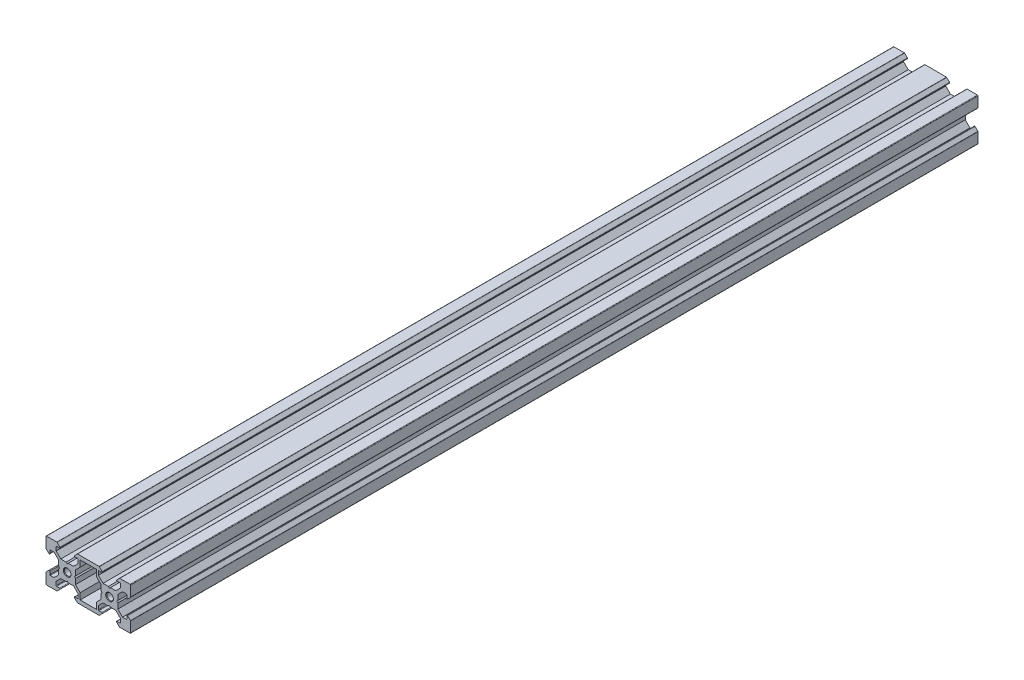
SolidWorks part; units mm, degrees
ref_plane "Alzado" through (0, 0, 0) normal (0, 0, 1) x (1, 0, 0)
ref_plane "Planta" through (0, 0, 0) normal (0, 1, 0) x (1, 0, 0)
ref_plane "Vista lateral" through (0, 0, 0) normal (1, 0, 0) x (0, 0, -1)
sketch "Croquis1" plane through (0, 0, 0) normal (0, 0, 1) x (1, 0, 0)
  line L0 (-10.0414, 10) -> (-10.0414, 8.2) construction
  line L1 (-13.8828, 8.2) -> (-6.2, 8.2)
  line L2 (-13.8828, -8.2) -> (-6.2, -8.2)
  line L4 (-4.8096, 9.9268) -> (-3.5096, 8.6268)
  line L5 (-3.6864, 8.2) -> (-5.0429, 8.2)
  line L6 (-5.2929, 7.95) -> (-5.2929, 6.2)
  line L13 (-14.8728, 8.2) -> (-16.6, 8.2)
  line L14 (-5.2929, 6.2) -> (-3.0929, 4)
  line L15 (-3.0929, 4) -> (-0.5828, 4)
  line L16 (-16.0828, 0.5) -> (-16.5828, 0)
  line L17 (-16.0828, 3.0101) -> (-16.0828, 0.5)
  line L18 (-13.8828, 5.2101) -> (-16.0828, 3.0101)
  line L19 (-13.8828, 8.2) -> (-13.8828, 5.2101)
  line L23 (-16.0828, -3.0101) -> (-16.0828, -0.5)
  line L24 (-16.0828, -0.5) -> (-16.5828, 0)
  line L25 (-13.8828, -5.2101) -> (-16.0828, -3.0101)
  line L26 (-13.8828, -8.2) -> (-13.8828, -5.2101)
  line L29 (-0.5828, 4) -> (-0.0828, 3.5)
  line L30 (-0.0828, 3.5) -> (0.4172, 4)
  line L31 (0.4172, 4) -> (2.9272, 4)
  line L32 (2.9272, 4) -> (5.1272, 6.2)
  line L33 (5.1272, 6.2) -> (5.1272, 7.95)
  line L34 (4.8772, 8.2) -> (3.5207, 8.2)
  line L35 (3.3439, 8.6268) -> (4.6439, 9.9268)
  line L36 (4.8207, 10) -> (9.6672, 10)
  line L37 (9.9172, 9.75) -> (9.9172, 4.9036)
  line L38 (9.8439, 4.7268) -> (8.5439, 3.4268)
  line L39 (8.1172, 3.6036) -> (8.1172, 4.9601)
  line L40 (7.8672, 5.2101) -> (6.1172, 5.2101)
  line L41 (6.1172, 5.2101) -> (3.9172, 3.0101)
  line L42 (3.9172, 3.0101) -> (3.9172, 0.5)
  line L43 (3.9172, 0.5) -> (3.4172, 0)
  line L44 (3.4172, 0) -> (3.9172, -0.5)
  line L45 (3.9172, -0.5) -> (3.9172, -3.0101)
  line L46 (3.9172, -3.0101) -> (6.1172, -5.2101)
  line L47 (6.1172, -5.2101) -> (7.8672, -5.2101)
  line L48 (8.1172, -4.9601) -> (8.1172, -3.6036)
  line L49 (8.5439, -3.4268) -> (9.8439, -4.7268)
  line L50 (9.9172, -4.9036) -> (9.9172, -9.75)
  line L51 (9.6672, -10) -> (4.8207, -10)
  line L52 (4.6439, -9.9268) -> (3.3439, -8.6268)
  line L53 (3.5207, -8.2) -> (4.8772, -8.2)
  line L54 (5.1272, -7.95) -> (5.1272, -6.2)
  line L55 (5.1272, -6.2) -> (2.9272, -4)
  line L56 (2.9272, -4) -> (0.4172, -4)
  line L57 (0.4172, -4) -> (-0.0828, -3.5)
  line L58 (-0.0828, -3.5) -> (-0.5828, -4)
  line L59 (-0.5828, -4) -> (-3.0929, -4)
  line L60 (-3.0929, -4) -> (-5.2929, -6.2)
  line L61 (-5.2929, -6.2) -> (-5.2929, -7.95)
  line L62 (-5.0429, -8.2) -> (-3.6864, -8.2)
  line L63 (-3.5096, -8.6268) -> (-4.8096, -9.9268)
  line L64 (-6.2, -8.2) -> (-6.2, -5.2101)
  line L65 (-6.2, -5.2101) -> (-4, -3.0101)
  line L66 (-4, -3.0101) -> (-4, -0.5)
  line L67 (-4, -0.5) -> (-3.5, 0)
  line L68 (-4, 0.5) -> (-3.5, 0)
  line L69 (-4, 3.0101) -> (-4, 0.5)
  line L70 (-6.2, 5.2101) -> (-4, 3.0101)
  line L71 (-6.2, 8.2) -> (-6.2, 5.2101)
  line L72 (-39.2829, 0) -> (29.3198, 0) construction
  line L73 (-20, 18.9047) -> (-20, -25.5585) construction
  line L74 (-0.0828, -25.5585) -> (-0.0828, 18.9047) construction
  line L164 (-26.2, 5.2101) -> (-24, 3.0101)
  line L165 (-24, 3.0101) -> (-24, 0.5)
  line L166 (-24, 0.5) -> (-23.5, 0)
  line L167 (-23.5, 0) -> (-24, -0.5)
  line L168 (-24, -0.5) -> (-24, -3.0101)
  line L169 (-24, -3.0101) -> (-26.2, -5.2101)
  line L170 (-26.2, -5.2101) -> (-27.95, -5.2101)
  line L171 (-28.2, -4.9601) -> (-28.2, -3.6036)
  line L172 (-28.6268, -3.4268) -> (-29.9268, -4.7268)
  line L173 (-30, -4.9036) -> (-30, -9.75)
  line L174 (-29.75, -10) -> (-24.9036, -10)
  line L175 (-24.7268, -9.9268) -> (-23.4268, -8.6268)
  line L176 (-23.6036, -8.2) -> (-24.9601, -8.2)
  line L177 (-25.2101, -7.95) -> (-25.2101, -6.2)
  line L178 (-25.2101, -6.2) -> (-23.0101, -4)
  line L179 (-23.0101, -4) -> (-20.5, -4)
  line L180 (-20.5, -4) -> (-20, -3.5)
  line L181 (-20, -3.5) -> (-19.5, -4)
  line L182 (-19.5, -4) -> (-16.9899, -4)
  line L183 (-16.9899, -4) -> (-14.7899, -6.2)
  line L184 (-14.7899, -6.2) -> (-14.7899, -7.95)
  line L185 (-15.0399, -8.2) -> (-16.3964, -8.2)
  line L186 (-16.5732, -8.6268) -> (-15.2732, -9.9268)
  line L187 (-15.0964, -10) -> (-4.9864, -10)
  line L228 (-4.9864, 10) -> (-15.0964, 10)
  line L229 (-15.2732, 9.9268) -> (-16.5732, 8.6268)
  line L230 (-16.3964, 8.2) -> (-15.0399, 8.2)
  line L231 (-14.7899, 7.95) -> (-14.7899, 6.2)
  line L232 (-14.7899, 6.2) -> (-16.9899, 4)
  line L233 (-16.9899, 4) -> (-19.5, 4)
  line L234 (-19.5, 4) -> (-20, 3.5)
  line L235 (-20, 3.5) -> (-20.5, 4)
  line L236 (-20.5, 4) -> (-23.0101, 4)
  line L237 (-23.0101, 4) -> (-25.2101, 6.2)
  line L238 (-25.2101, 6.2) -> (-25.2101, 7.95)
  line L239 (-24.9601, 8.2) -> (-23.6036, 8.2)
  line L240 (-23.4268, 8.6268) -> (-24.7268, 9.9268)
  line L241 (-24.9036, 10) -> (-29.75, 10)
  line L242 (-30, 9.75) -> (-30, 4.9036)
  line L243 (-29.9268, 4.7268) -> (-28.6268, 3.4268)
  line L244 (-28.2, 3.6036) -> (-28.2, 4.9601)
  line L245 (-27.95, 5.2101) -> (-26.2, 5.2101)
  arc A0 (-3.5096, 8.6268) -> (-3.6864, 8.2) centre (-3.6864, 8.45) cw
  arc A1 (-15.0964, 10) -> (-15.2732, 9.9268) centre (-15.0964, 9.75) ccw
  arc A2 (-15.0399, 8.2) -> (-14.7899, 7.95) centre (-15.0399, 7.95) cw
  arc A4 (-16.5732, 8.6268) -> (-16.3964, 8.2) centre (-16.3964, 8.45) ccw
  arc A6 (-14.7899, -7.95) -> (-15.0399, -8.2) centre (-15.0399, -7.95) cw
  arc A7 (-16.3964, -8.2) -> (-16.5732, -8.6268) centre (-16.3964, -8.45) ccw
  arc A8 (-15.2732, -9.9268) -> (-15.0964, -10) centre (-15.0964, -9.75) ccw
  arc A9 (-24.9601, -8.2) -> (-25.2101, -7.95) centre (-24.9601, -7.95) cw
  arc A10 (-23.4268, -8.6268) -> (-23.6036, -8.2) centre (-23.6036, -8.45) ccw
  arc A11 (-24.9036, -10) -> (-24.7268, -9.9268) centre (-24.9036, -9.75) ccw
  arc A12 (-30, -9.75) -> (-29.75, -10) centre (-29.75, -9.75) ccw
  arc A13 (-29.9268, -4.7268) -> (-30, -4.9036) centre (-29.75, -4.9036) ccw
  arc A14 (-28.2, -3.6036) -> (-28.6268, -3.4268) centre (-28.45, -3.6036) ccw
  arc A15 (-27.95, -5.2101) -> (-28.2, -4.9601) centre (-27.95, -4.9601) cw
  arc A16 (-24.7268, 9.9268) -> (-24.9036, 10) centre (-24.9036, 9.75) ccw
  arc A17 (-23.6036, 8.2) -> (-23.4268, 8.6268) centre (-23.6036, 8.45) ccw
  arc A18 (-25.2101, 7.95) -> (-24.9601, 8.2) centre (-24.9601, 7.95) cw
  arc A19 (-28.2, 4.9601) -> (-27.95, 5.2101) centre (-27.95, 4.9601) cw
  arc A20 (-28.6268, 3.4268) -> (-28.2, 3.6036) centre (-28.45, 3.6036) ccw
  arc A21 (-30, 4.9036) -> (-29.9268, 4.7268) centre (-29.75, 4.9036) ccw
  arc A22 (-29.75, 10) -> (-30, 9.75) centre (-29.75, 9.75) ccw
  arc A23 (-5.0429, 8.2) -> (-5.2929, 7.95) centre (-5.0429, 7.95) ccw
  arc A24 (5.1272, 7.95) -> (4.8772, 8.2) centre (4.8772, 7.95) ccw
  arc A25 (3.5207, 8.2) -> (3.3439, 8.6268) centre (3.5207, 8.45) cw
  arc A26 (4.6439, 9.9268) -> (4.8207, 10) centre (4.8207, 9.75) cw
  arc A27 (9.6672, 10) -> (9.9172, 9.75) centre (9.6672, 9.75) cw
  arc A28 (9.9172, 4.9036) -> (9.8439, 4.7268) centre (9.6672, 4.9036) cw
  arc A29 (8.5439, 3.4268) -> (8.1172, 3.6036) centre (8.3672, 3.6036) cw
  arc A30 (8.1172, 4.9601) -> (7.8672, 5.2101) centre (7.8672, 4.9601) ccw
  arc A31 (7.8672, -5.2101) -> (8.1172, -4.9601) centre (7.8672, -4.9601) ccw
  arc A32 (8.1172, -3.6036) -> (8.5439, -3.4268) centre (8.3672, -3.6036) cw
  arc A33 (9.8439, -4.7268) -> (9.9172, -4.9036) centre (9.6672, -4.9036) cw
  arc A34 (9.9172, -9.75) -> (9.6672, -10) centre (9.6672, -9.75) cw
  arc A35 (4.8207, -10) -> (4.6439, -9.9268) centre (4.8207, -9.75) cw
  arc A36 (3.3439, -8.6268) -> (3.5207, -8.2) centre (3.5207, -8.45) cw
  arc A37 (4.8772, -8.2) -> (5.1272, -7.95) centre (4.8772, -7.95) ccw
  arc A38 (-5.2929, -7.95) -> (-5.0429, -8.2) centre (-5.0429, -7.95) ccw
  arc A39 (-3.6864, -8.2) -> (-3.5096, -8.6268) centre (-3.6864, -8.45) cw
  arc A40 (-4.8096, -9.9268) -> (-4.9864, -10) centre (-4.9864, -9.75) cw
  arc A41 (-4.9864, 10) -> (-4.8096, 9.9268) centre (-4.9864, 9.75) cw
  point P47 (-10.0414, -8.2)
  point P134 (-10.0414, 8.2)
  dimension "D1" = 0.25
  dimension "D2" = 19.9172
extrude "Saliente-Extruir1" add sketch "Croquis1" along normal blind 200 and the other way blind 200 contours A41 L228 L1 L71 L70 L69 L68 L67 L66 L65 L64 L2 L26 L25 L23 L24 L16 L17 L18 L19 A1 L229 A4 L13 A2 L231 L232 L233 L234 L235 L236 L237 L238 A18 L239 A17 L240 A16 L241 A22 L242 A21 L243 A20 L244 region at (-4.4753, 8.9611, 0)
sketch "Croquis4" plane through (0, 0, 200) normal (0, 0, 1) x (1, 0, 0)
  line L0 (-24.6708, 0) -> (6.8007, 0) construction
  line L1 (-20, 3.5) -> (-20, 0) construction
  circle A0 centre (-20, 0) radius 1.5693
  circle A1 centre (0, 0) radius 1.5693
extrude "Cortar-Extruir1" cut sketch "Croquis4" against normal through all
chamfer "Chaflán1" distance 0.25 angle 45 4 edges at (-18.4307, 0, -200) (1.5693, 0, -200) (1.5693, 0, 200) (-18.4307, 0, 200)
sketch "Croquis5" plane through (0, 10, 0) normal (0, 1, 0) x (1, 0, 0)
  line L0 (-4.9864, 200) -> (-15.0964, 200) construction
  line L1 (-10.0414, 200) -> (-10.0414, 160.25) construction
  line L2 (-34.8345, 160.25) -> (22.5535, 160.25) construction
  line L3 (-20, 200) -> (-20, -200) construction
  line L4 (-0.0828, 200) -> (-0.0828, -200) construction
  point P8 (-20, 160.25)
  point P9 (-0.0828, 160.25)
  dimension "D1" = 39.75
hole_wizard "Taladro roscado M31" positions "Croquis6" profile "Croquis8" tap size "M3" standard "DIN" end condition through all
sketch "Croquis6" plane through (0, 10, 0) normal (0, 1, 0) x (1, 0, 0)
  point P0 (-20, 160.25)
  point P3 (-0.0828, 160.25)
sketch "Croquis8" plane through (-20, 10, -160.25) normal (1, 0, 0) x (0, 0, 1)
  line L0 (0, 0) -> (0, 20)
  line L1 (0, 20) -> (1.25, 20)
  line L2 (1.25, 20) -> (1.25, 0)
  line L5 (1.25, 0) -> (0, 0)
  line L11 (0, -6.35) -> (0, 107.95) construction
  dimension "Diámetro de perforador para roscar hasta el siguiente" = 2.5
  dimension "Profundidad de perforador para roscar hasta el siguiente" = 20
cosmetic thread "Rosca de taladro1" parameters "D2"=3
ref_plane "Plano1" through (0, 10, 0) normal (0, 1, 0) x (1, 0, 0)
ref_plane "Plano2" through (0, -10, 0) normal (0, -1, 0) x (-1, 0, 0)
ref_plane "Plano3" through (-30, 0, 0) normal (-1, 0, 0) x (0, 0, 1)
sketch "Croquis10" plane through (-30, 0, 0) normal (-1, 0, 0) x (0, 0, 1)
  line L0 (-213.3304, 0) -> (229.9435, 0) construction
ref_plane "Plano4" through (9.9172, 0, 0) normal (1, 0, 0) x (0, 0, -1)
